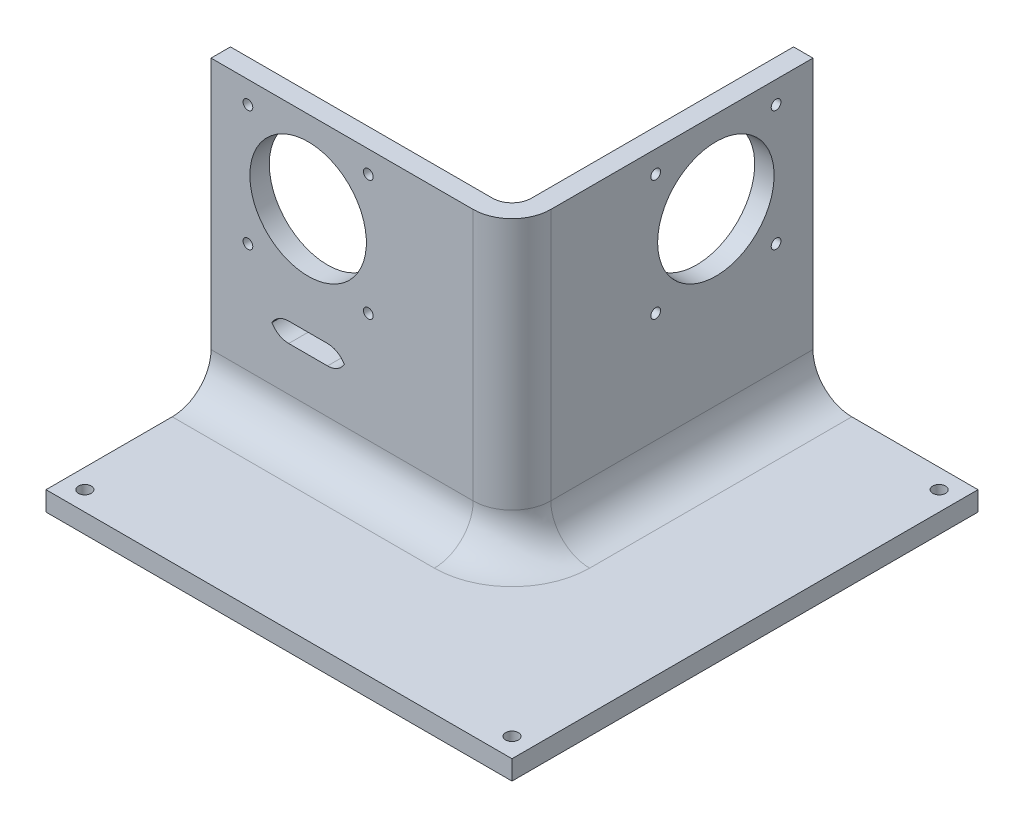
SolidWorks part; units mm, degrees
ref_plane "Front Plane" through (0, 0, 0) normal (0, 0, 1) x (1, 0, 0)
ref_plane "Top Plane" through (0, 0, 0) normal (0, 1, 0) x (1, 0, 0)
ref_plane "Right Plane" through (0, 0, 0) normal (1, 0, 0) x (0, 0, -1)
sketch "Sketch1" plane through (0, 0, 0) normal (0, 1, 0) x (1, 0, 0)
  line L0 (0, 72.5) -> (0, 0)
  line L1 (-72.5, -72.5) -> (72.5, -72.5)
  line L2 (-72.5, -72.5) -> (-72.5, 72.5)
  line L3 (-72.5, 72.5) -> (72.5, 72.5)
  line L4 (72.5, -72.5) -> (72.5, 72.5)
  line L5 (-72.5, -72.5) -> (72.5, 72.5) construction
  line L6 (-72.5, 72.5) -> (72.5, -72.5) construction
  line L7 (0, 0) -> (-72.5, 0)
  line L8 (-72.5, 0) -> (-72.5, -72.5)
  point P0 (0, 0)
  dimension "D1" = 145
  dimension "D2" = 145
extrude "Boss-Extrude1" add sketch "Sketch1" along normal blind 20 contours L0 L7 L2 L1 L4 L3 region at (12.0833, 0, 12.0833)
sketch "Sketch2" plane through (0, 20, 0) normal (0, 1, 0) x (1, 0, 0)
  line L0 (0, 72.5) -> (72.5, 72.5) construction
  line L1 (0, 0) -> (5, 0)
  line L2 (0, 0) -> (0, 72.5)
  line L3 (0, 72.5) -> (5, 72.5)
  line L4 (5, 0) -> (5, 72.5)
  line L5 (0, 0) -> (5, 72.5) construction
  line L6 (0, 72.5) -> (5, 0) construction
  line L7 (0, 0) -> (-72.5, 0) construction
  line L8 (0, 72.5) -> (0, 0) construction
  point P0 (2.5, 36.25)
  dimension "D1" = 0
  dimension "D2" = 0
  dimension "D3" = 0
  dimension "D4" = 5
extrude "Boss-Extrude2" add sketch "Sketch2" along normal blind 60
sketch "Sketch3" plane through (0, 0, 0) normal (-1, 0, 0) x (0, 0, 1)
  line L0 (-72.5, 80) -> (0, 80) construction
  line L1 (-72.5, 80) -> (-72.5, 0) construction
  circle A0 centre (-47.5, 58.85) radius 15
  dimension "D3" = 30
  dimension "D1" = 21.15
  dimension "D2" = 25
extrude "Cut-Extrude1" cut sketch "Sketch3" against normal blind 100
sketch "Sketch4" plane through (0, 0, 0) normal (-1, 0, 0) x (0, 0, 1)
  circle A0 centre (-32, 74.35) radius 1.25
  circle A1 centre (-63, 74.35) radius 1.25
  circle A2 centre (-63, 43.35) radius 1.25
  circle A3 centre (-32, 43.35) radius 1.25
  circle A5 centre (-32, 74.35) radius 1.2294 construction
  circle A7 centre (-32, 74.35) radius 1.5 construction
  circle A8 centre (-63, 74.35) radius 1.2294 construction
  circle A9 centre (-32, 43.35) radius 1.5 construction
  dimension "D1" = 0
  dimension "D3" = 2.5
  dimension "D6" = 2.5
  dimension "D9" = 2.5
  dimension "D12" = 2.5
  dimension "D2" = 0
  dimension "D4" = 0
  dimension "D5" = 0
  dimension "D7" = 0
  dimension "D8" = 0
  dimension "D10" = 0
  dimension "D11" = 0
extrude "Cut-Extrude2" cut sketch "Sketch4" against normal blind 100
sketch "Sketch7" plane through (0, 20, 0) normal (0, 1, 0) x (1, 0, 0)
  line L1 (-72.5, 0) -> (5, 0)
  line L2 (-72.5, 0) -> (-72.5, -5)
  line L3 (-72.5, -5) -> (5, -5)
  line L4 (5, 0) -> (5, -5)
  dimension "D1" = 5
  dimension "D2" = 0
extrude "Boss-Extrude6" add sketch "Sketch7" along normal blind 60
ref_plane "Plane2" through (0, 0, 0) normal (-0.7071, 0, 0.7071) x (0.7071, 0, 0.7071)
mirror "Mirror5" about plane through (0, 0, 0) normal (-0.7071, 0, 0.7071) of "Cut-Extrude2", "Cut-Extrude1"
fillet "Fillet3" radius 5 1 edges at (0, 40, 0)
sketch "Sketch8" plane through (0, 20, 0) normal (0, 1, 0) x (1, 0, 0)
  line L0 (-72.5, -72.5) -> (72.5, -72.5) construction
  line L1 (47.5, -72.5) -> (72.5, -72.5)
  line L2 (47.5, -72.5) -> (47.5, 72.5)
  line L3 (47.5, 72.5) -> (72.5, 72.5)
  line L4 (72.5, -72.5) -> (72.5, 72.5)
  line L5 (47.5, -72.5) -> (72.5, 72.5) construction
  line L6 (47.5, 72.5) -> (72.5, -72.5) construction
  line L7 (72.5, -47.5) -> (-72.5, -47.5)
  line L8 (72.5, -47.5) -> (72.5, -72.5)
  line L9 (72.5, -72.5) -> (-72.5, -72.5)
  line L10 (-72.5, -47.5) -> (-72.5, -72.5)
  line L11 (72.5, -47.5) -> (-72.5, -72.5) construction
  line L12 (72.5, -72.5) -> (-72.5, -47.5) construction
  point P0 (60, 0)
  point P6 (0, -60)
  line M7 (-72.5, -5) -> (-72.5, -72.5)
  line M8 (-72.5, -72.5) -> (72.5, -72.5)
  line M9 (72.5, -72.5) -> (72.5, 72.5)
  line M10 (72.5, 72.5) -> (5, 72.5)
  dimension "D1" = 0
  dimension "D2" = 0
  dimension "D3" = 25
  dimension "D4" = 25
extrude "Cut-Extrude3" cut sketch "Sketch8" against normal blind 100 contours L7 L4 L2 M10 | L7 L2 M9 M8 | L2 L7 M7 M8 region at (60, 20, 60) region at (-12.5, 20, 60) region at (60, 20, -12.5)
sketch "Sketch9" plane through (0, 20, 0) normal (0, 1, 0) x (1, 0, 0)
  line L0 (47.5, -47.5) -> (47.5, 72.5) construction
  line L1 (5, 72.5) -> (47.5, 72.5) construction
  line L2 (47.5, -47.5) -> (-72.5, -47.5) construction
  line L4 (-72.5, -47.5) -> (-72.5, -5) construction
  circle A0 centre (42.5, 67.5) radius 1.65
  circle A1 centre (42.5, -42.5) radius 1.65
  circle A2 centre (-67.5, -42.5) radius 1.65
  dimension "D3" = 3.3
  dimension "D6" = 3.3
  dimension "D8" = 3.3
  dimension "D1" = 5
  dimension "D2" = 5
  dimension "D4" = 0
  dimension "D5" = 5
  dimension "D7" = 0
  dimension "D9" = 5
extrude "Cut-Extrude4" cut sketch "Sketch9" against normal blind 100
sketch "Sketch10" plane through (0, 20, 0) normal (0, 1, 0) x (1, 0, 0)
  line L0 (-72.5, -5) -> (5, -5) construction
  line L1 (47.5, -47.5) -> (5, -47.5)
  line L2 (47.5, -47.5) -> (47.5, 72.5)
  line L3 (47.5, 72.5) -> (5, 72.5)
  line L4 (5, -47.5) -> (5, 72.5)
  line L5 (47.5, -47.5) -> (5, 72.5) construction
  line L6 (47.5, 72.5) -> (5, -47.5) construction
  line L7 (47.5, -5) -> (-72.5, -5)
  line L8 (47.5, -5) -> (47.5, -47.5)
  line L9 (47.5, -47.5) -> (-72.5, -47.5)
  line L10 (-72.5, -5) -> (-72.5, -47.5)
  line L11 (47.5, -5) -> (-72.5, -47.5) construction
  line L12 (47.5, -47.5) -> (-72.5, -5) construction
  line L13 (47.5, -47.5) -> (47.5, 72.5) construction
  point P0 (26.25, 12.5)
  point P6 (-12.5, -26.25)
  dimension "D1" = 0
  dimension "D2" = 0
  dimension "D3" = 0
  dimension "D4" = 0
extrude "Cut-Extrude5" cut sketch "Sketch10" against normal blind 15 contours L2 L1 L4 L3 | L8 L7 L10 L9
fillet "Fillet4" radius 10 3 edges at (5, 42.5, 5) (-33.75, 5, 5) (5, 5, -33.75)
sketch "Sketch11" plane through (0, 0, 5) normal (0, 0, 1) x (1, 0, 0)
  line L1 (-57.5, 26.35) -> (-37.5, 26.35)
  line L2 (-57.5, 26.35) -> (-57.5, 31.35)
  line L3 (-57.5, 31.35) -> (-37.5, 31.35)
  line L4 (-37.5, 26.35) -> (-37.5, 31.35)
  line L5 (-57.5, 26.35) -> (-37.5, 31.35) construction
  line L6 (-57.5, 31.35) -> (-37.5, 26.35) construction
  circle A0 centre (-47.5, 58.85) radius 15 construction
  point P0 (-47.5, 28.85)
  dimension "D1" = 0
  dimension "D2" = 30
  dimension "D3" = 5
  dimension "D4" = 20
extrude "Cut-Extrude6" cut sketch "Sketch11" against normal blind 6
fillet "Fillet5" radius 5 4 edges at (-57.5, 26.35, 2.5) (-57.5, 31.35, 2.5) (-37.5, 31.35, 2.5) (-37.5, 26.35, 2.5)
